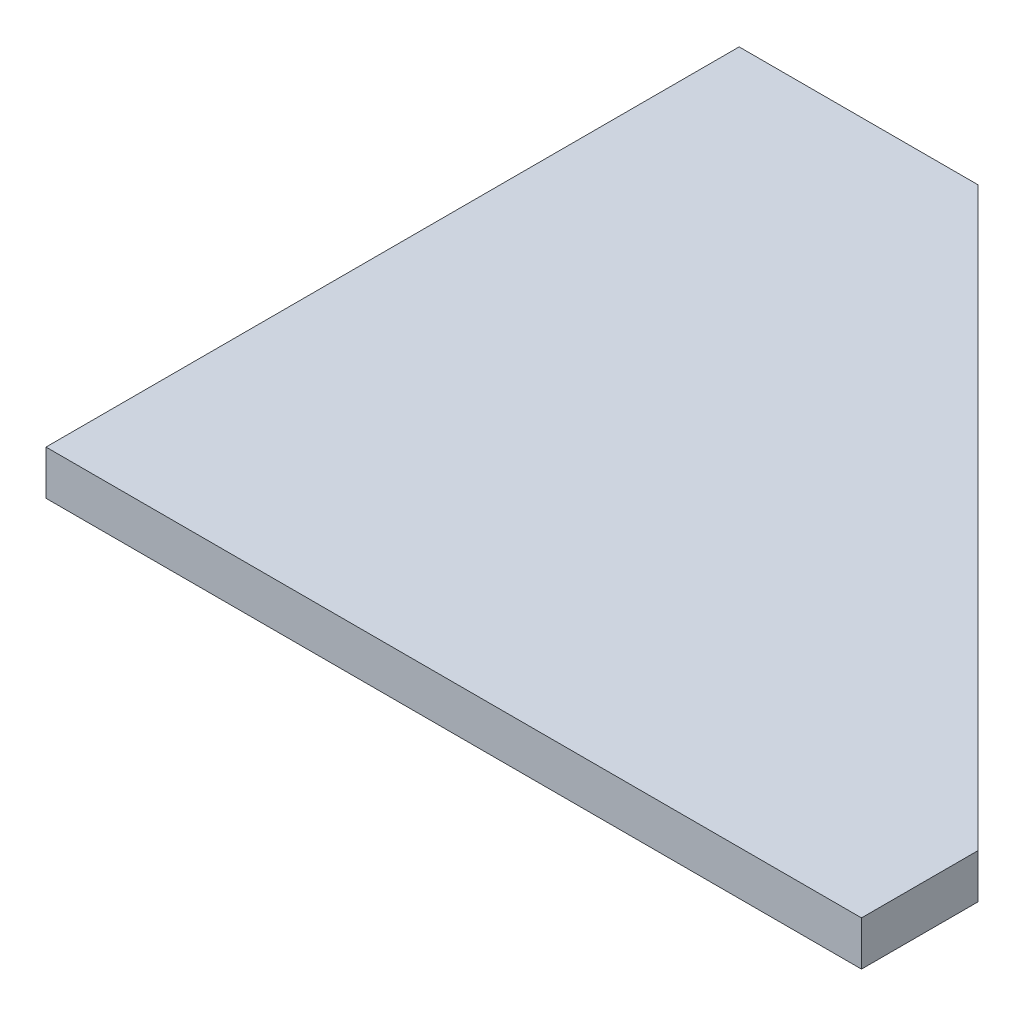
SolidWorks part; units mm, degrees
ref_plane "Front Plane" through (0, 0, 0) normal (0, 0, 1) x (1, 0, 0)
ref_plane "Top Plane" through (0, 0, 0) normal (0, 1, 0) x (1, 0, 0)
ref_plane "Right Plane" through (0, 0, 0) normal (1, 0, 0) x (0, 0, -1)
sketch "Sketch1" plane through (0, 0, 0) normal (0, 1, 0) x (1, 0, 0)
  line L0 (-144.97, 297.485) -> (350, -197.485)
  line L1 (-350, 297.485) -> (-144.97, 297.485)
  line L2 (-350, 297.485) -> (-350, -297.485)
  line L3 (-350, -297.485) -> (350, -297.485)
  line L4 (350, -197.485) -> (350, -297.485)
  line L5 (-350, 297.485) -> (350, -297.485) construction
  point P0 (0, 0)
  dimension "D1" = 594.97
  dimension "D2" = 700
  dimension "D3" = 100
  dimension "D4" = 45
extrude "Boss-Extrude1" add sketch "Sketch1" along normal blind 38.1
sketch "Sketch2" plane through (0, 0, 0) normal (0, -1, 0) x (1, 0, 0)
  line L5 (-350, -297.485) -> (-350, 297.485) construction
  line L6 (-350, -107.485) -> (-331, -107.485)
  line L7 (-350, -107.485) -> (-350, -157.485)
  line L8 (-350, -157.485) -> (-331, -157.485)
  line L9 (-331, -107.485) -> (-331, -157.485)
  line L10 (-144.97, -297.485) -> (-350, -297.485) construction
  line L11 (-350, 0) -> (152.515, 0) construction
  line L12 (350, 197.485) -> (-144.97, -297.485) construction
  line L13 (-331, 107.485) -> (-331, 157.485)
  line L14 (-350, 157.485) -> (-331, 157.485)
  line L15 (-350, 107.485) -> (-350, 157.485)
  line L16 (-350, 107.485) -> (-331, 107.485)
  dimension "D1" = 50
  dimension "D2" = 19
  dimension "D3" = 140
extrude "Cut-Extrude1" cut sketch "Sketch2" against normal blind 2
sketch "Sketch3" plane through (0, 0, 0) normal (0, 1, 0) x (1, 0, 0)
  line L0 (-144.97, 297.485) -> (-186.7165, 255.7385)
  line L1 (-186.7165, 255.7385) -> (-151.5041, 221.6877)
  line L2 (-151.5041, 221.6877) -> (-111.0289, 263.5439)
  line L3 (350, -197.485) -> (-144.97, 297.485) construction
  line L4 (-111.0289, 263.5439) -> (-144.97, 297.485)
  dimension "D1" = 48
extrude "Cut-Extrude2" cut sketch "Sketch3" along normal blind 20
